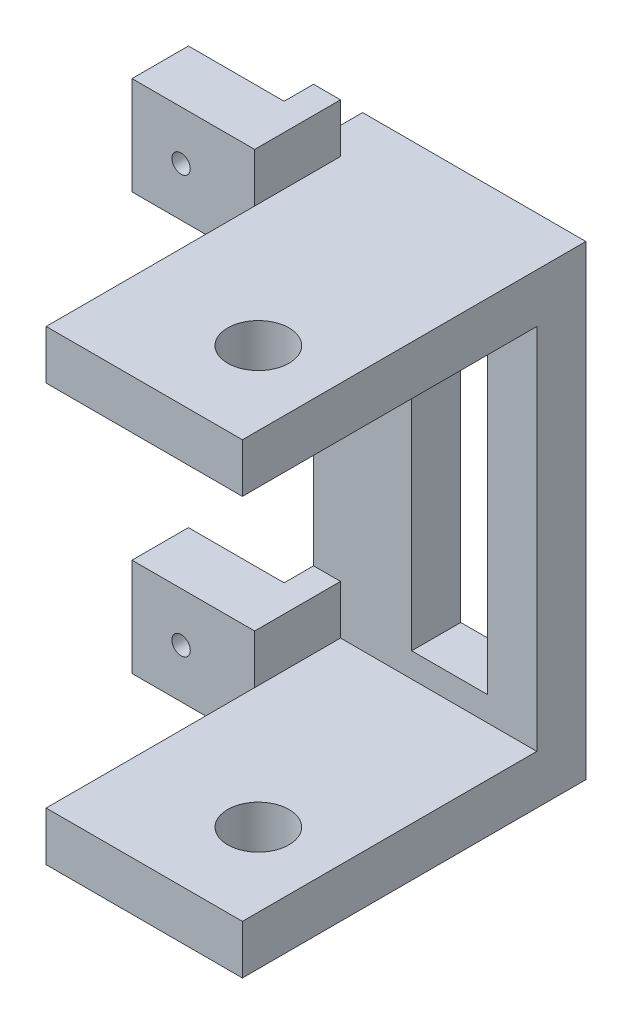
SolidWorks part; units mm, degrees
ref_plane "前视基准面" through (0, 0, 0) normal (0, 0, 1) x (1, 0, 0)
ref_plane "上视基准面" through (0, 0, 0) normal (0, 1, 0) x (1, 0, 0)
ref_plane "右视基准面" through (0, 0, 0) normal (1, 0, 0) x (0, 0, -1)
sketch "草图2" plane through (0, 0, 0) normal (0, 0, 1) x (1, 0, 0)
  line L3 (-5.9, -9.5) -> (6.1, -9.5)
  line L4 (6.1, 9.5) -> (6.1, -9.5)
  line L5 (0, 0) -> (2.4933, 0) construction
  line L6 (0, 0) -> (0, -3.9686) construction
  line L15 (-5.9, 9.5) -> (6.1, 9.5)
  line L20 (-5.9, 9.5) -> (-5.9, -9.5)
  line L21 (1, 6.5) -> (4.1, 6.5)
  line L23 (1, -6.5) -> (1, 6.5)
  line L26 (4.1, 6.5) -> (4.1, -6.5)
  line L28 (1, -6.5) -> (4.1, -6.5)
  point P0 (0, 0)
  dimension "D1" = 12
  dimension "D2" = 3.1
  dimension "D3" = 19
  dimension "D4" = 3
  dimension "D9" = 2
extrude "凸台-拉伸1" add sketch "草图2" along normal blind 2
sketch "草图3" plane through (0, 0, 2) normal (0, 0, 1) x (1, 0, 0)
  line L1 (-1.9, 9.5) -> (6.1, 9.5)
  line L2 (-1.9, 9.5) -> (-1.9, 7.5)
  line L3 (-1.9, 7.5) -> (6.1, 7.5)
  line L4 (6.1, 9.5) -> (6.1, 7.5)
  line L5 (6.1, -9.5) -> (6.1, 9.5) construction
  line L6 (-1.9, -7.5) -> (6.1, -7.5)
  line L8 (-1.9, -9.5) -> (6.1, -9.5)
  line L9 (6.1, -7.5) -> (6.1, -9.5)
  line L10 (-5.9, -9.5) -> (6.1, -9.5) construction
  line L11 (-1.9, -7.5) -> (-1.9, -9.5)
  line L12 (6.1, 9.5) -> (-5.9, 9.5) construction
  dimension "D1" = 2
  dimension "D2" = 2
  dimension "D3" = 8
  dimension "D4" = 8
extrude "凸台-拉伸2" add sketch "草图3" along normal blind 12
sketch "草图10" plane through (0, 0, 2) normal (0, 0, 1) x (1, 0, 0)
  line L9 (-6.9, 11.5) -> (-1.9, 11.5)
  line L10 (-6.9, 11.5) -> (-6.9, 7.5)
  line L11 (-6.9, 7.5) -> (-1.9, 7.5)
  line L12 (-1.9, 11.5) -> (-1.9, 7.5)
  line L13 (-6.9, -5.5) -> (-1.9, -5.5)
  line L14 (-6.9, -5.5) -> (-6.9, -9.5)
  line L15 (-6.9, -9.5) -> (-1.9, -9.5)
  line L16 (-1.9, -5.5) -> (-1.9, -9.5)
  line L17 (-1.9, -7.5) -> (-1.9, -9.5) construction
  line L19 (-1.9, 9.5) -> (-1.9, 7.5) construction
  line L20 (-1.9, 7.5) -> (6.1, 7.5) construction
  line L23 (-5.9, -9.5) -> (-1.9, -9.5) construction
  dimension "D1" = 4
  dimension "D2" = 5
extrude "凸台-拉伸4" add sketch "草图10" along normal blind 3.5
sketch "草图9" plane through (0, 0, 2) normal (0, 0, 1) x (1, 0, 0)
  line L3 (-6.9, 11.5) -> (-6.9, 7.5) construction
  line L4 (-4.9, 9.5) -> (-4.9, -7.5) construction
  line L5 (6.1, 9.5) -> (-1.9, 9.5) construction
  line L9 (6.1, -7.5) -> (-1.9, -7.5) construction
  circle A0 centre (-4.9, 9.5) radius 0.375
  circle A1 centre (-4.9, -7.5) radius 0.375
  point P4 (0, 0)
  point P9 (0, 0)
  point P10 (-10.8713, 1.8602)
  point P11 (0, 0)
  point P14 (0, 0)
  dimension "D1" = 0.75
  dimension "D2" = 0.75
  dimension "D4" = 2
extrude "切除-拉伸2" cut sketch "草图9" against normal up to next from surface starting at face at (-3.9, 9.5, 5.5)
sketch "草图11" plane through (0, -9.5, 0) normal (0, -1, 0) x (1, 0, 0)
  line L0 (-1.9, 14) -> (-1.9, 5.5) construction
  line L1 (-1.9, 14) -> (6.1, 14) construction
  circle A0 centre (3.1, 10.35) radius 1.25
  dimension "D1" = 2.5
  dimension "D2" = 5
  dimension "D3" = 3.65
extrude "切除-拉伸3" cut sketch "草图11" against normal through all
sketch "草图12" plane through (0, -9.5, 0) normal (0, -1, 0) x (1, 0, 0)
  line L0 (-6.9, 5.5) -> (-6.9, 2) construction
  line L1 (-6.9, 3.2) -> (-3, 3.2)
  line L2 (-6.9, 3.2) -> (-6.9, 0)
  line L3 (-6.9, 0) -> (-3, 0)
  line L4 (-3, 3.2) -> (-3, 0)
  line L5 (-5.9, 0) -> (6.1, 0) construction
  line L6 (-3.1, 3.1) -> (-6.9, 3.1) construction
  line L7 (-3.1, 0.1) -> (-3.1, 3.1) construction
  dimension "D1" = 0.1
  dimension "D2" = 0.1
extrude "切除-拉伸4" cut sketch "草图12" against normal up to next
